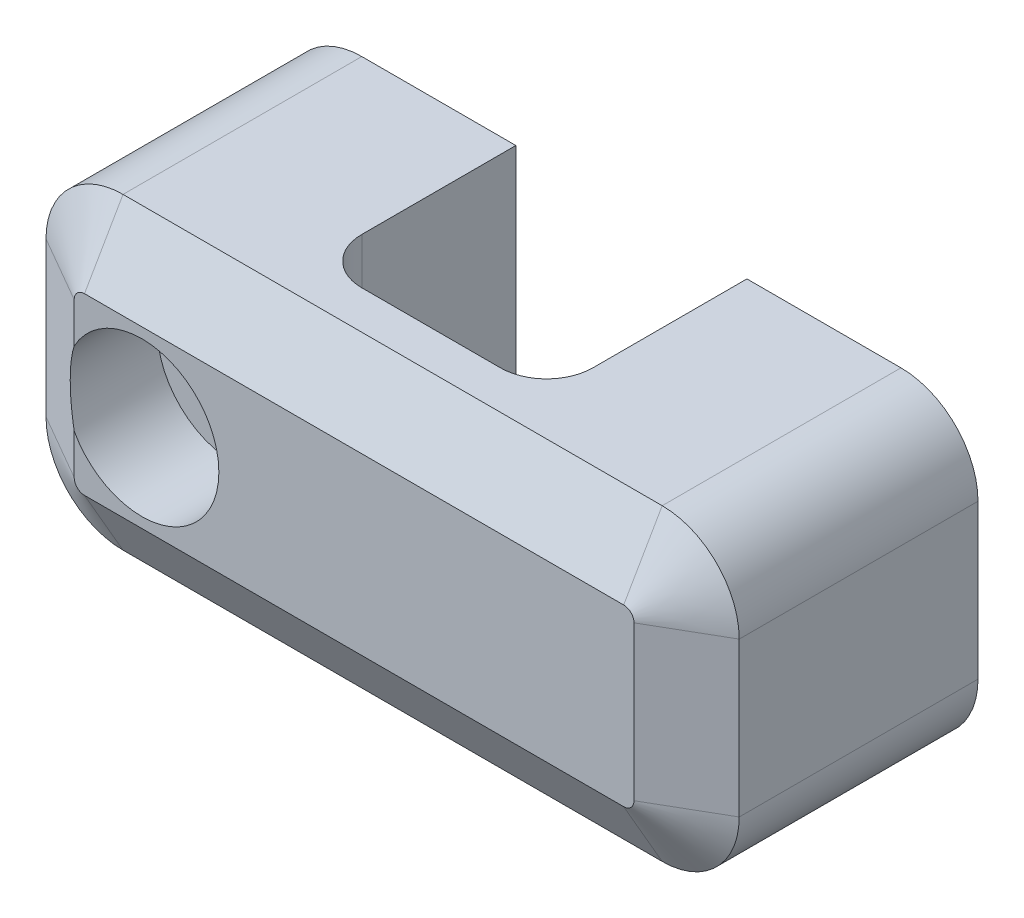
SolidWorks part; units mm, degrees
ref_plane "Front Plane" through (0, 0, 0) normal (0, 0, 1) x (1, 0, 0)
ref_plane "Top Plane" through (0, 0, 0) normal (0, 1, 0) x (1, 0, 0)
ref_plane "Right Plane" through (0, 0, 0) normal (1, 0, 0) x (0, 0, -1)
sketch "Sketch1" plane through (0, 0, 0) normal (0, 0, 1) x (1, 0, 0)
  line L1 (22.5, -10) -> (-22.5, -10)
  line L2 (22.5, -10) -> (22.5, 10)
  line L3 (22.5, 10) -> (-22.5, 10)
  line L4 (-22.5, -10) -> (-22.5, 10)
  line L5 (22.5, -10) -> (-22.5, 10) construction
  line L6 (22.5, 10) -> (-22.5, -10) construction
  point P0 (0, 0)
  dimension "D1" = 45
  dimension "D2" = 20
extrude "Extrude1" add sketch "Sketch1" along normal blind 5
sketch "Sketch2" plane through (0, 0, 0) normal (0, 0, -1) x (-1, 0, 0)
  line L0 (22.5, -10) -> (-22.5, -10) construction
  line L1 (22.5, 10) -> (7.5, 10)
  line L2 (22.5, 10) -> (22.5, -10)
  line L3 (22.5, -10) -> (7.5, -10)
  line L4 (7.5, 10) -> (7.5, -10)
  line L5 (0, -10) -> (0, 19.479) construction
  line L6 (-7.5, 10) -> (-7.5, -10)
  line L7 (-22.5, -10) -> (-7.5, -10)
  line L8 (-22.5, 10) -> (-22.5, -10)
  line L9 (-22.5, 10) -> (-7.5, 10)
  dimension "D1" = 15
extrude "Extrude2" add sketch "Sketch2" along normal blind 13
sketch "Sketch3" plane through (0, 0, 5) normal (0, 0, 1) x (1, 0, 0)
  line L0 (0, 0) -> (-24.4612, 0) construction
  circle A0 centre (-13.7784, 0) radius 5
  point P3 (-13.7784, 0)
extrude "Extrude3" cut sketch "Sketch3" against normal blind 6
sketch "Sketch4" plane through (0, 0, -1) normal (0, 0, 1) x (1, 0, 0)
  circle A0 centre (-13.7784, 0) radius 2.5
  dimension "D1" = 5
extrude "Extrude4" cut sketch "Sketch4" against normal blind 16
fillet "Fillet1" radius 5 4 edges at (-22.5, -10, -4) (-22.5, 10, -4) (22.5, -10, -4) (22.5, 10, -4)
chamfer "Chamfer1" distance 2.5 angle 60 8 edges at (0, -10, 5) (-21.0355, -8.5355, 5) (-22.5, 0, 5) (-21.0355, 8.5355, 5) (0, 10, 5) (22.5, 0, 5) (21.0355, -8.5355, 5) (21.0355, 8.5355, 5)
ref_plane "Plane1" through (-7.5, 10, 0) normal (0, -1, 0) x (-1, 0, 0)
fillet "Fillet2" radius 3 2 edges
fillet "Fillet3" radius 3 1 edges at (7.5, 0, 0)
